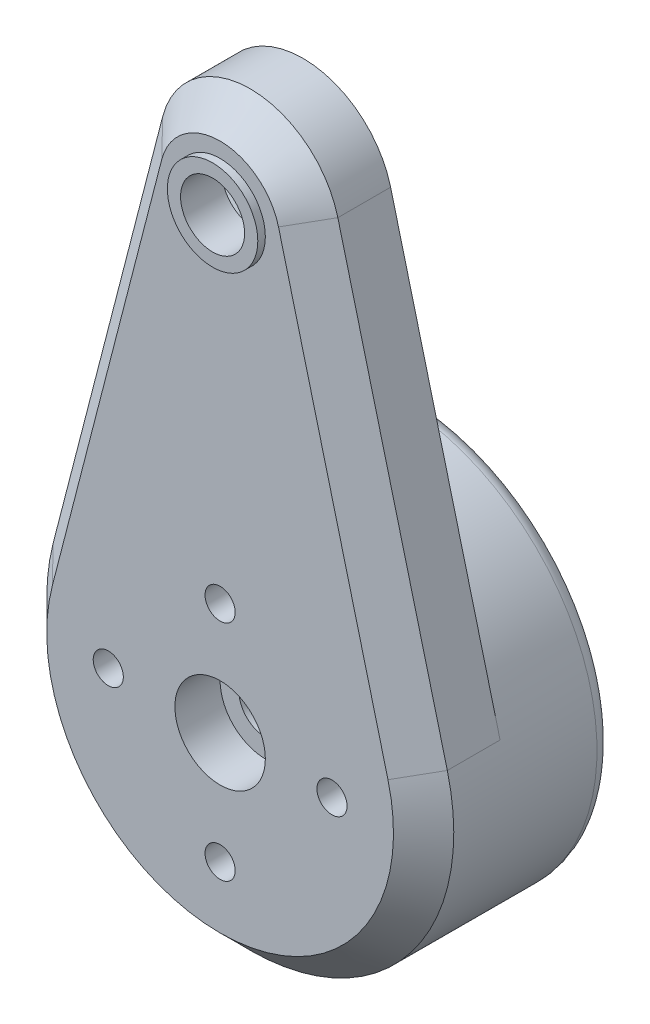
SolidWorks part; units mm, degrees
ref_plane "Front Plane" through (0, 0, 0) normal (0, 0, 1) x (1, 0, 0)
ref_plane "Top Plane" through (0, 0, 0) normal (0, 1, 0) x (1, 0, 0)
ref_plane "Right Plane" through (0, 0, 0) normal (1, 0, 0) x (0, 0, -1)
sketch "Sketch1" plane through (0, 0, 0) normal (0, 0, 1) x (1, 0, 0)
  line L0 (0, 0) -> (0, 30) construction
  line L1 (-13.0713, 3.375) -> (-5.8095, 31.5)
  line L2 (5.8095, 31.5) -> (13.0713, 3.375)
  arc A0 (-13.0713, 3.375) -> (13.0713, 3.375) centre (0, 0) ccw
  arc A1 (5.8095, 31.5) -> (-5.8095, 31.5) centre (0, 30) ccw
  circle A2 centre (0, 30) radius 2.125
  circle A3 centre (0, 0) radius 10
  circle A4 centre (0, 0) radius 1.625
  dimension "D1" = 27
  dimension "D3" = 12
  dimension "D4" = 4.25
  dimension "D5" = 20
  dimension "D6" = 3.25
  dimension "D2" = 30
extrude "Boss-Extrude1" add sketch "Sketch1" along normal blind 5.5 contours A3 | L2 A1 L1 A0 A3 A2 | A4 region at (0, 12.4311, 0) region at (-9.7172, 0, 0) region at (0, 0, 0)
sketch "Sketch4" plane through (0, 0, 0) normal (0, 0, -1) x (-1, 0, 0)
  circle A4 centre (0, 0) radius 13.5
  arc A5 (-13.0713, 3.375) -> (13.0713, 3.375) centre (0, 0) ccw construction
extrude "Boss-Extrude2" add sketch "Sketch4" along normal blind 7
sketch "Sketch6" plane through (0, 0, -7) normal (0, 0, -1) x (-1, 0, 0)
  circle A0 centre (0, 0) radius 11
  dimension "D1" = 22
extrude "Cut-Extrude4" cut sketch "Sketch6" against normal blind 4
sketch "Sketch5" plane through (0, 0, -3) normal (0, 0, -1) x (-1, 0, 0)
  line L0 (0, 0) -> (7.42, 0) construction
  circle A0 centre (7.42, 0) radius 1
  circle A1 centre (0, -7.42) radius 1
  circle A2 centre (-7.42, 0) radius 1
  circle A3 centre (0, 7.42) radius 1
  circle A4 centre (0, 0) radius 7.42 construction
  circle A5 centre (0, 0) radius 1.75
  point P5 (0, 0)
  point P12 (0, 0)
  point P14 (0, 0)
  dimension "D2" = 2
  dimension "D1" = 14.84
  dimension "D4" = 3.5
  dimension "D3" = 4
extrude "Cut-Extrude2" cut sketch "Sketch5" against normal through all
chamfer "Chamfer1" distance 2 angle 45 4 edges at (0, -13.5, 5.5) (-9.4404, 17.4375, 5.5) (0, 36, 5.5) (9.4404, 17.4375, 5.5)
sketch "Sketch7" plane through (0, 0, 5.5) normal (0, 0, 1) x (1, 0, 0)
  circle A0 centre (0, 0) radius 3
  dimension "D1" = 6
extrude "Cut-Extrude5" cut sketch "Sketch7" against normal blind 3
fillet "Fillet1" radius 1 1 edges at (-13.5, 0, -7)
sketch "Sketch8" plane through (0, 0, 5.5) normal (0, 0, 1) x (1, 0, 0)
  circle A0 centre (0, 30) radius 3
  circle A2 centre (0, 30) radius 2.125 construction
  circle A3 centre (0, 30) radius 2.125
  dimension "D1" = 6
extrude "Boss-Extrude3" add sketch "Sketch8" along normal blind 0.5
sketch "Sketch9" plane through (0, 0, 0) normal (0, 0, -1) x (-1, 0, 0)
  line L1 (0, 25.6699) -> (3.75, 27.8349)
  line L2 (3.75, 27.8349) -> (3.75, 32.1651)
  line L3 (3.75, 32.1651) -> (0, 34.3301)
  line L4 (0, 34.3301) -> (-3.75, 32.1651)
  line L5 (-3.75, 32.1651) -> (-3.75, 27.8349)
  line L6 (-3.75, 27.8349) -> (0, 25.6699)
  circle A0 centre (0, 30) radius 3.75 construction
  dimension "D1" = 7.5
extrude "Cut-Extrude6" cut sketch "Sketch9" against normal blind 3.25
fillet "Fillet2" radius 0.5 6 edges at (3.75, 30, 0) (1.875, 26.7524, 0) (-1.875, 26.7524, 0) (-3.75, 30, 0) (-1.875, 33.2476, 0) (1.875, 33.2476, 0)
